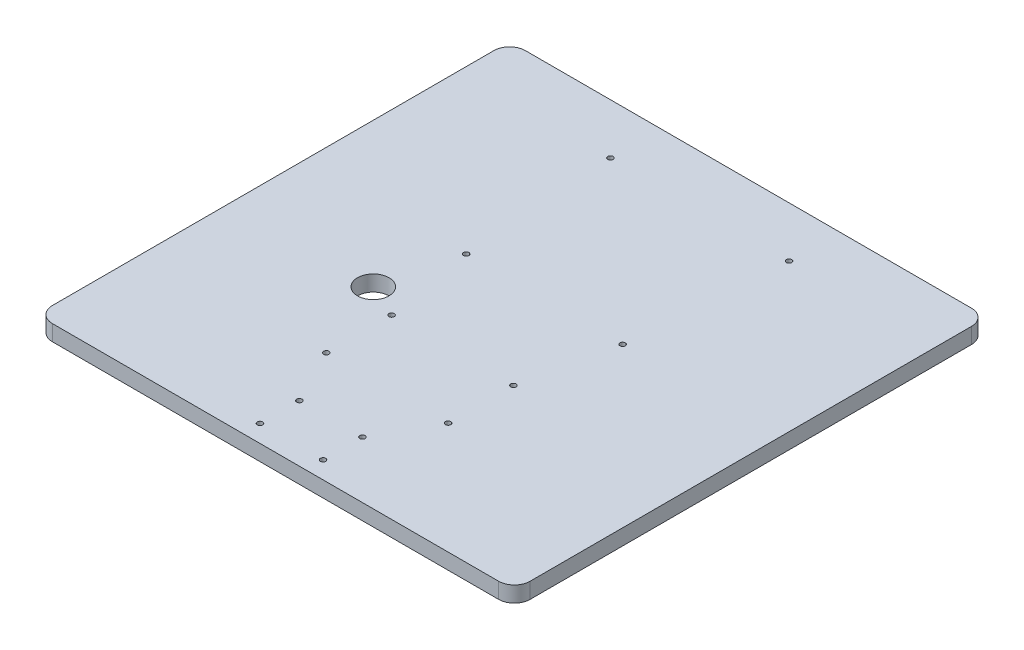
SolidWorks part; units mm, degrees
note: The reader was unsure of these and kept them because the rebuilt part matched: thickness of "Base-Flange1", "Sheet-Metal(1)", "Sheet-Metal(15)", "Sheet-Metal(16)", "Sheet-Metal(17)", "Sheet-Metal(18)".
material "Plain Carbon Steel"
ref_plane "Front Plane" through (0, 0, 0) normal (0, 0, 1) x (1, 0, 0)
ref_plane "Top Plane" through (0, 0, 0) normal (0, 1, 0) x (1, 0, 0)
ref_plane "Right Plane" through (0, 0, 0) normal (1, 0, 0) x (0, 0, -1)
sketch "Sketch1" plane through (0, 0, 0) normal (0, 1, 0) x (1, 0, 0)
  line L0 (151.5, 300) -> (151.5, 0) construction
  line L1 (0, 0) -> (303, 0)
  line L2 (0, 0) -> (0, 300)
  line L3 (0, 300) -> (303, 300)
  line L4 (303, 0) -> (303, 300)
  dimension "D1" = 300
  dimension "D2" = 303
base flange "Base-Flange1" sketch "Sketch1" thickness 10 reverse thickness direction no parameters "D1"=0.762
ref_plane "Plane1" through (151.5, 0, 0) normal (1, 0, 0) x (0, 0, -1)
fillet "Fillet1" radius 10 4 edges at (303, -5, 0) (0, -5, 0) (303, -5, -300) (0, -5, -300)
sketch "Sketch18" plane through (0, 0, 0) normal (0, 1, 0) x (1, 0, 0)
  line L0 (216.5, 140) -> (86.5, 140)
  line L1 (86.5, 140) -> (86.5, 300)
  line L2 (86.5, 300) -> (216.5, 300)
  line L3 (151.5, -55.3673) -> (151.5, 55.3673) construction
  line L4 (293, 300) -> (10, 300) construction
  line L5 (86.5, 220) -> (216.5, 220)
  line L6 (216.5, 140) -> (216.5, 300)
  dimension "D1" = 0
  dimension "D2" = 130
  dimension "D3" = 160
  dimension "D4" = 65
sketch "RetrievalArm" plane through (0, 0, 0) normal (0, 1, 0) x (1, 0, 0)
  line L1 (293, 300) -> (10, 300) construction
  line L2 (0, 290) -> (0, 10) construction
  circle A0 centre (25, 275) radius 12
  circle A1 centre (25, 275) radius 140
  dimension "D1" = 25
  dimension "D2" = 25
ref_plane "Plane4" through (-51.7, 0, 0) normal (1, 0, 0) x (0, 0, -1)
sketch "Sketch24" plane through (0, 0, 0) normal (0, 1, 0) x (1, 0, 0)
  line L0 (90.625, 40) -> (212.375, 40)
  line L1 (212.375, 40) -> (212.375, 0)
  line L2 (212.375, 0) -> (90.625, 0)
  line L3 (90.625, 0) -> (90.625, 40)
  line L4 (151.5, -55.3673) -> (151.5, 55.3673) construction
  line L5 (10, 0) -> (293, 0) construction
  dimension "D1" = 60.875
  dimension "D2" = 40
  dimension "D3" = 121.75
  dimension "D4" = 0
hole_wizard "M3 Clearance Hole1" positions "Sketch26" profile "Sketch25" hole size "M3" standard "ANSI Metric"
sketch "Sketch26" plane through (0, 0, 0) normal (0, 1, 0) x (1, 0, 0)
  point P0 (202.2366, 169.4697)
  point P3 (102.9732, 169.4697)
  point P6 (95.9732, 267.9965)
  point P9 (209.2366, 267.9965)
sketch "Sketch25" plane through (202.2366, 0, -169.4697) normal (1, 0, 0) x (0, 0, 1)
  line L0 (0, 0) -> (0, 51.0215)
  line L1 (0, 51.0215) -> (1.7, 50)
  line L2 (1.7, 50) -> (1.7, 0)
  line L5 (1.7, 0) -> (0, 0)
  line L10 (0, 51.0215) -> (-1.7, 50) construction
  line L11 (0, -6.35) -> (0, 107.95) construction
  dimension "Hole Dia." = 3.4
  dimension "Hole Depth" = 50
  dimension "Drill Angle" = 118
sketch "WireHole" plane through (0, 0, 0) normal (0, 1, 0) x (1, 0, 0)
  line L0 (10, 0) -> (293, 0) construction
  line L1 (151.5, -55.3673) -> (151.5, 55.3673) construction
  circle A0 centre (91.5, 122) radius 10
  dimension "D1" = 122
  dimension "D2" = 60
hole_wizard "M3 Clearance Hole2" positions "Sketch28" profile "Sketch27" hole size "M3" standard "ANSI Metric"
sketch "Sketch28" plane through (0, 0, 0) normal (0, 1, 0) x (1, 0, 0)
  point P0 (130.625, 11)
  point P3 (170.625, 11)
  point P6 (130.625, 36)
  point P9 (170.625, 36)
sketch "Sketch27" plane through (130.625, 0, -11) normal (1, 0, 0) x (0, 0, 1)
  line L0 (0, 0) -> (0, 29.7315)
  line L1 (0, 29.7315) -> (1.7, 28.71)
  line L2 (1.7, 28.71) -> (1.7, 0)
  line L5 (1.7, 0) -> (0, 0)
  line L10 (0, 29.7315) -> (-1.7, 28.71) construction
  line L11 (0, -6.35) -> (0, 107.95) construction
  dimension "Hole Dia." = 3.4
  dimension "Hole Depth" = 28.71
  dimension "Drill Angle" = 118
sketch "Sketch30" plane through (0, 0, 0) normal (0, 1, 0) x (1, 0, 0)
  line L0 (151.5, -55.3673) -> (151.5, 55.3673) construction
  line L1 (197.15, 60) -> (105.85, 60)
  line L2 (197.15, 60) -> (197.15, 121.3)
  line L3 (197.15, 121.3) -> (105.85, 121.3)
  line L4 (105.85, 60) -> (105.85, 121.3)
  line L5 (197.15, 60) -> (105.85, 121.3) construction
  line L6 (197.15, 121.3) -> (105.85, 60) construction
  line L7 (90.625, 40) -> (212.375, 40) construction
  point P0 (151.5, 90.65)
  dimension "D1" = 61.3
  dimension "D2" = 91.3
  dimension "D3" = 45.65
  dimension "D4" = 20
extrude "Cut-Extrude1" cut sketch "WireHole" against normal blind 10 contours A0 normal cut yes
hole_wizard "M3 Clearance Hole3" positions "Sketch32" profile "Sketch31" hole size "M3" standard "ANSI Metric"
sketch "Sketch32" plane through (0, 0, 0) normal (0, 1, 0) x (1, 0, 0)
  point P0 (190.15, 70.852)
  point P3 (190.15, 112.248)
  point P6 (112.86, 70.852)
  point P9 (112.86, 112.248)
sketch "Sketch31" plane through (190.15, 0, -70.852) normal (1, 0, 0) x (0, 0, 1)
  line L0 (0, 0) -> (0, 29.7315)
  line L1 (0, 29.7315) -> (1.7, 28.71)
  line L2 (1.7, 28.71) -> (1.7, 0)
  line L5 (1.7, 0) -> (0, 0)
  line L10 (0, 29.7315) -> (-1.7, 28.71) construction
  line L11 (0, -6.35) -> (0, 107.95) construction
  dimension "Hole Dia." = 3.4
  dimension "Hole Depth" = 28.71
  dimension "Drill Angle" = 118
sketch "Sketch33" plane through (0, -10, 0) normal (0, -1, 0) x (-1, 0, 0)
  line L0 (-221.5, 300) -> (-221.5, 209.502)
  line L1 (-293, 300) -> (-10, 300) construction
  line L2 (-303, 10) -> (-303, 290) construction
  dimension "D1" = 81.5
sketch "Bend-Lines1" plane through (0, 0, 0) normal (0, 1, 0) x (1, 0, 0)
sketch "Bounding-Box1" plane through (0, 0, 0) normal (0, 1, 0) x (1, 0, 0)
sheet metal parameters "Sheet-Metal(1)" thickness 10 parameters "D1"=0.762
flat pattern "Flat-Pattern(1)" [suppressed]
sketch "Bend-Lines2" plane through (0, 0, 0) normal (0, 1, 0) x (1, 0, 0)
sketch "Bounding-Box2" [suppressed] plane through (0, 0, 0) normal (0, 1, 0) x (1, 0, 0)
sheet metal parameters "Sheet-Metal(15)" thickness 10 parameters "D1"=0.762
flat pattern "Flat-Pattern(1)"
sketch "Bend-Lines2" plane through (0, 0, 0) normal (0, 1, 0) x (1, 0, 0)
sketch "Bounding-Box2" [suppressed] plane through (0, 0, 0) normal (0, 1, 0) x (1, 0, 0)
sheet metal parameters "Sheet-Metal(16)" thickness 10 parameters "D1"=0.762
flat pattern "Flat-Pattern(1)"
sketch "Bend-Lines2" plane through (0, 0, 0) normal (0, 1, 0) x (1, 0, 0)
sketch "Bounding-Box2" [suppressed] plane through (0, 0, 0) normal (0, 1, 0) x (1, 0, 0)
sheet metal parameters "Sheet-Metal(17)" thickness 10 parameters "D1"=0.762
flat pattern "Flat-Pattern(1)"
sketch "Bend-Lines2" plane through (0, 0, 0) normal (0, 1, 0) x (1, 0, 0)
sketch "Bounding-Box2" [suppressed] plane through (0, 0, 0) normal (0, 1, 0) x (1, 0, 0)
sheet metal parameters "Sheet-Metal(18)" thickness 10 parameters "D1"=0.762
flat pattern "Flat-Pattern(1)"
sketch "Bend-Lines2" plane through (0, 0, 0) normal (0, 1, 0) x (1, 0, 0)
sketch "Bounding-Box2" [suppressed] plane through (0, 0, 0) normal (0, 1, 0) x (1, 0, 0)
